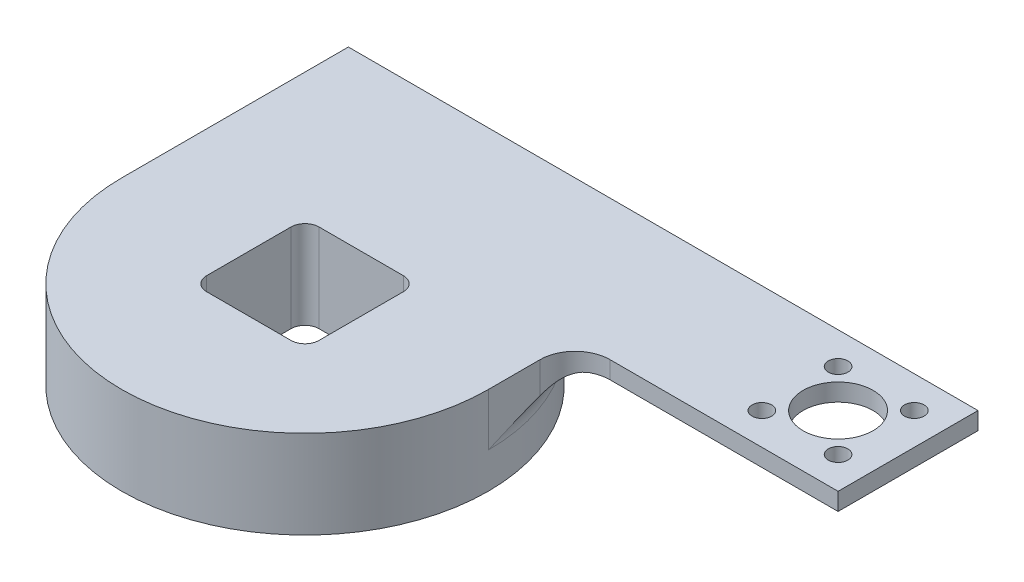
SolidWorks part; units mm, degrees
ref_plane "Front Plane" through (0, 0, 0) normal (0, 0, 1) x (1, 0, 0)
ref_plane "Top Plane" through (0, 0, 0) normal (0, 1, 0) x (1, 0, 0)
ref_plane "Right Plane" through (0, 0, 0) normal (1, 0, 0) x (0, 0, -1)
sketch "Sketch1" plane through (0, 0, 0) normal (0, 1, 0) x (1, 0, 0)
  line L0 (-1.1049, 0) -> (-33.274, 0) construction
  line L1 (-1.1049, 0) -> (33.274, 0) construction
  circle A0 centre (0, 0) radius 33.274
extrude "Boss-Extrude1" add sketch "Sketch1" along normal blind 16.002
sketch "Sketch2" plane through (0, 16.002, 0) normal (0, 1, 0) x (1, 0, 0)
  line L0 (0, 0) -> (-33.274, 0) construction
  line L1 (0, 0) -> (33.274, 0) construction
  line L2 (-33.274, 0) -> (-33.274, 41.148)
  line L3 (-33.274, 41.148) -> (81.026, 41.148)
  line L4 (81.026, 41.148) -> (81.026, 15.748)
  line L5 (33.274, 0) -> (33.274, 15.748)
  line L6 (33.274, 15.748) -> (81.026, 15.748)
  circle A0 centre (0, 0) radius 33.274 construction
  circle A2 centre (0, 0) radius 33.274
  arc A3 (-33.274, 0) -> (33.274, 0) centre (0, 0) ccw
  dimension "D1" = 0
extrude "Boss-Extrude2" add sketch "Sketch2" against normal blind 3.175
fillet "Fillet1" radius 6.35 1 edges at (0, 12.827, -33.274)
fillet "Fillet2" radius 6.35 1 edges at (33.274, 14.0863, -15.748)
sketch "Sketch4" plane through (0, 16.002, 0) normal (0, 1, 0) x (1, 0, 0)
  line L0 (81.026, 41.148) -> (58.166, 41.148) construction
  line L1 (81.026, 41.148) -> (-33.274, 41.148) construction
  line L2 (58.166, 41.148) -> (58.166, 28.448) construction
  line L3 (58.166, 28.448) -> (78.486, 28.448) construction
  line L4 (68.326, 28.448) -> (75.2408, 35.3628) construction
  line L5 (68.326, 28.448) -> (75.2408, 21.5332) construction
  line L6 (68.326, 28.448) -> (61.4112, 21.5332) construction
  line L7 (68.326, 28.448) -> (61.4112, 35.3628) construction
  circle A0 centre (61.4112, 35.3628) radius 1.778
  circle A1 centre (75.2408, 35.3628) radius 1.778
  circle A2 centre (75.2408, 21.5332) radius 1.778
  circle A3 centre (68.326, 28.448) radius 6.35
  circle A4 centre (61.4112, 21.5332) radius 1.778
extrude "Cut-Extrude2" cut sketch "Sketch4" against normal up to next
sketch "Sketch5" plane through (0, 16.002, 0) normal (0, 1, 0) x (1, 0, 0)
  line L1 (10.1926, 10.1926) -> (-10.1926, 10.1926)
  line L2 (10.1926, 10.1926) -> (10.1926, -10.1926)
  line L3 (10.1926, -10.1926) -> (-10.1926, -10.1926)
  line L4 (-10.1926, 10.1926) -> (-10.1926, -10.1926)
  line L5 (10.1926, 10.1926) -> (-10.1926, -10.1926) construction
  line L6 (10.1926, -10.1926) -> (-10.1926, 10.1926) construction
  point P0 (0, 0)
  dimension "D1" = 28.829
extrude "Cut-Extrude3" cut sketch "Sketch5" against normal up to next
fillet "Fillet3" radius 2.54 1 edges at (-10.1926, 8.001, -10.1926)
fillet "Fillet4" radius 2.54 1 edges at (10.1926, 8.001, -10.1926)
fillet "Fillet5" radius 2.54 1 edges at (10.1926, 8.001, 10.1926)
fillet "Fillet6" radius 2.54 1 edges at (-10.1926, 8.001, 10.1926)
